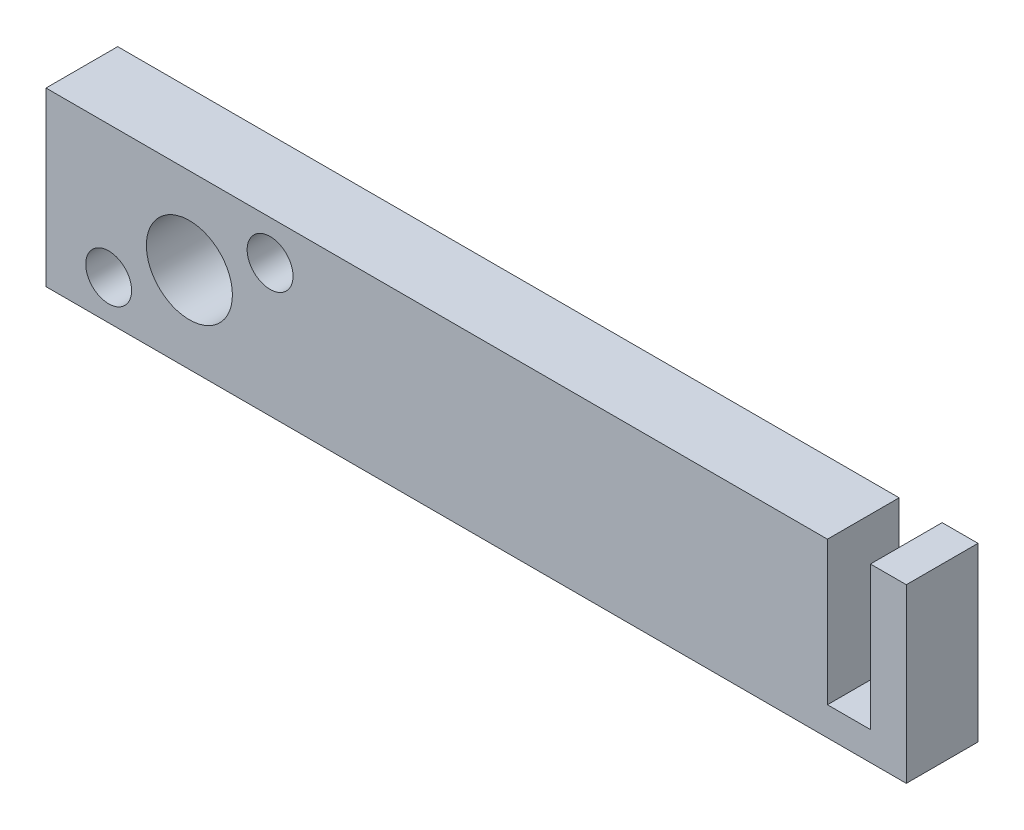
SolidWorks part; units mm, degrees
ref_plane "正面" through (0, 0, 0) normal (0, 0, 1) x (1, 0, 0)
ref_plane "平面" through (0, 0, 0) normal (0, 1, 0) x (1, 0, 0)
ref_plane "右側面" through (0, 0, 0) normal (1, 0, 0) x (0, 0, -1)
sketch "ｽｹｯﾁ1" plane through (0, 0, 0) normal (0, 0, 1) x (1, 0, 0)
  line L0 (0, 0) -> (10, 0)
  line L1 (0, 0) -> (5.6292, 3.25)
  line L2 (0, 0) -> (-5.6292, -3.25)
  line L3 (0, 0) -> (0, -6)
  line L4 (0, -6) -> (50, -6)
  line L5 (50, -6) -> (50, 6)
  line L6 (50, 6) -> (47.5, 6)
  line L7 (-10, 6) -> (-10, -6)
  line L8 (-10, -6) -> (0, -6)
  line L9 (50, 6) -> (47.5, 6)
  line L10 (47.5, 6) -> (47.5, -4)
  line L11 (47.5, -4) -> (44.5, -4)
  line L12 (44.5, -4) -> (44.5, 6)
  line L13 (44.5, 6) -> (-10, 6)
  circle A0 centre (0, 0) radius 3
  circle A1 centre (5.6292, 3.25) radius 1.6
  circle A2 centre (-5.6292, -3.25) radius 1.6
  dimension "D4" = 6
  dimension "D5" = 3.2
  dimension "D6" = 3.2
  dimension "D1" = 10
  dimension "D2" = 6.5
  dimension "D3" = 6.5
  dimension "D7" = 6
  dimension "D8" = 50
  dimension "D9" = 12
  dimension "D10" = 60
  dimension "D11" = 2.5
  dimension "D12" = 10
  dimension "D13" = 3
extrude "ﾎﾞｽ - 押し出し1" add sketch "ｽｹｯﾁ1" along normal blind 5 contours A2 A0 A1 L4 L5 L6 L10 L11 L12 L13 L7 L8 region at (20.166, -0.0465, 0)
